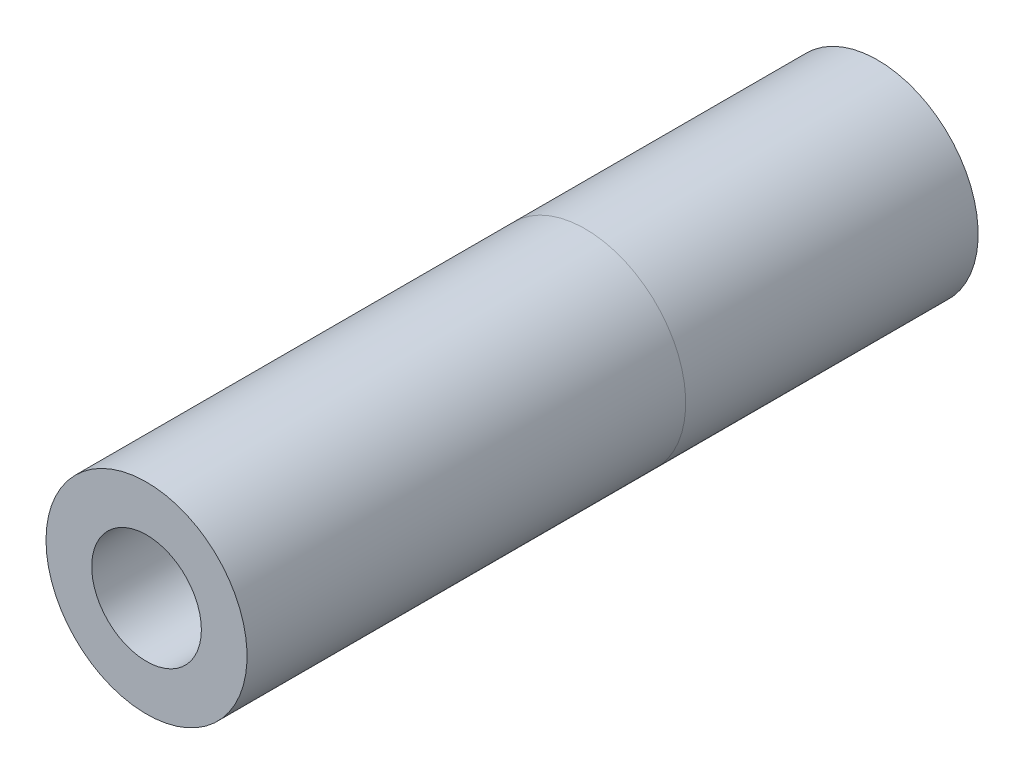
SolidWorks part; units mm, degrees
material "Silicon Rubber"
ref_plane "X-Y Datum" through (0, 0, 0) normal (0, 0, 1) x (1, 0, 0)
ref_plane "X-Z Datum" through (0, 0, 0) normal (0, 1, 0) x (1, 0, 0)
ref_plane "Y-Z Datum" through (0, 0, 0) normal (1, 0, 0) x (0, 0, -1)
sketch3d "3DSketch1"
  line L0 (0, 0, 0) -> (0, 0, 25.4)
  line L1 (0, 0, 25.4) -> (0, 0, 63.5)
  dimension "D1" = 25.4
  dimension "D2" = 38.1
sweep "Sweep1" add path "3DSketch1" circular profile diameter 17.4625 parameters "D3"=17.4625
sweep "Cut-Sweep1" cut path "3DSketch1<2>" circular profile diameter 9.525 parameters "D3"=9.525
sketch3d "3DSketch1<2>" same geometry as "3DSketch1"
sketch3d "3DSketch3"
  line L0 (0, 0, 0) -> (0, 0, 25.4) construction
  line L1 (0, 0, 38.1) -> (0, -4.7625, 38.1)
  line L2 (0, 0, 38.1) -> (-4.7625, 0, 38.1)
  circle A0 centre (0, 0, 38.1) radius 4.7625
  circle A3 centre (0, 0, 63.5) radius 4.7625 construction
  point P3 (0, 0, 33.3375)
  point P11 (0, 0, 58.7375)
  dimension "D1" = 25.4
